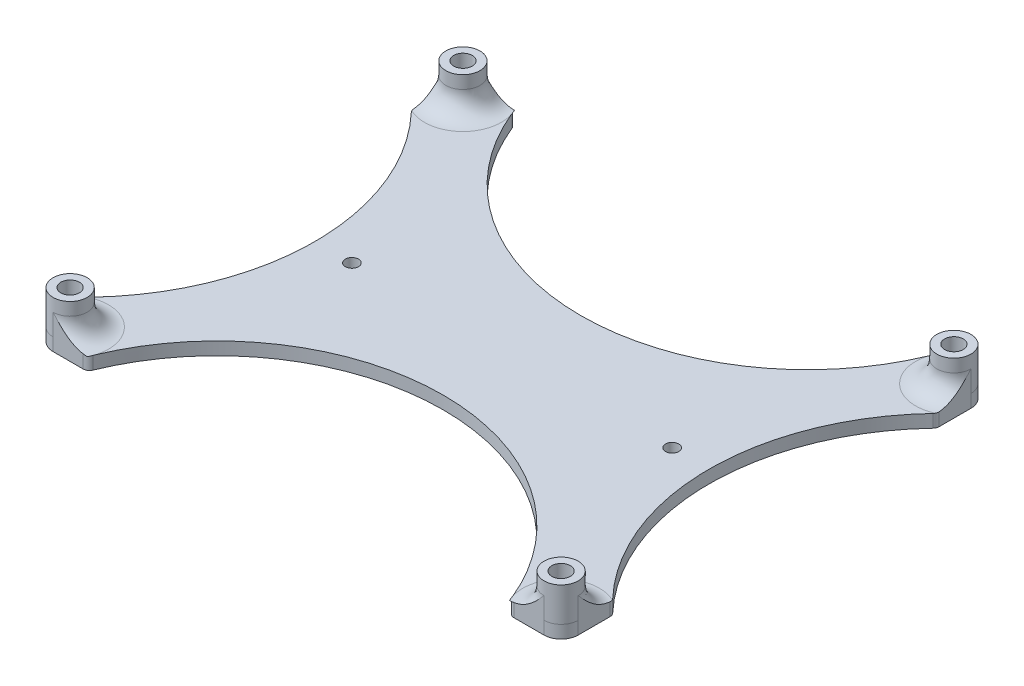
SolidWorks part; units mm, degrees
ref_plane "Alzado" through (0, 0, 0) normal (0, 0, 1) x (1, 0, 0)
ref_plane "Planta" through (0, 0, 0) normal (0, 1, 0) x (1, 0, 0)
ref_plane "Vista lateral" through (0, 0, 0) normal (1, 0, 0) x (0, 0, -1)
sketch "Croquis1" plane through (0, 0, 0) normal (0, 1, 0) x (1, 0, 0)
  line L1 (0, 0) -> (123, 0)
  line L2 (0, 0) -> (0, 100)
  line L3 (0, 100) -> (123, 100)
  line L4 (123, 0) -> (123, 100)
  dimension "D1" = 123
  dimension "D2" = 100
extrude "Saliente-Extruir1" add sketch "Croquis1" along normal blind 3
sketch "Croquis2" plane through (0, 3, 0) normal (0, 1, 0) x (1, 0, 0)
  line L0 (61.5, 100) -> (61.5, 0) construction
  line L1 (123, 100) -> (0, 100) construction
  line L2 (0, 0) -> (123, 0) construction
  line L3 (123, 0) -> (123, 100) construction
  line L4 (4, 4) -> (119, 4) construction
  line L5 (4, 4) -> (4, 96) construction
  line L6 (4, 96) -> (119, 96) construction
  line L7 (119, 4) -> (119, 96) construction
  line L8 (4, 4) -> (119, 96) construction
  line L9 (4, 96) -> (119, 4) construction
  circle A0 centre (4, 96) radius 4
  circle A1 centre (4, 4) radius 4
  circle A2 centre (119, 4) radius 4
  circle A3 centre (119, 96) radius 4
  point P6 (61.5, 50)
  dimension "D1" = 115
  dimension "D2" = 92
extrude "Saliente-Extruir2" add sketch "Croquis2" along normal blind 8
sketch "Croquis3" plane through (0, 11, 0) normal (0, 1, 0) x (1, 0, 0)
  circle A0 centre (4, 4) radius 4 construction
  circle A1 centre (4, 96) radius 4
  circle A2 centre (4, 96) radius 4
  arc A3 (123, 4) -> (119, 0) centre (119, 4) ccw construction
  arc A4 (119, 100) -> (123, 96) centre (119, 96) ccw construction
  circle A5 centre (4, 4) radius 4
  arc A6 (123, 4) -> (119, 0) centre (119, 4) ccw
  arc A7 (119, 100) -> (123, 96) centre (119, 96) ccw
  circle A8 centre (4, 96) radius 2.175
  circle A9 centre (119, 96) radius 2.175
  circle A10 centre (119, 4) radius 2.175
  circle A11 centre (4, 4) radius 2.175
  dimension "D2" = 4.35
  dimension "D1" = 0
extrude "Cortar-Extruir1" cut sketch "Croquis3" against normal blind 4.5 contours A8 | A9 | A10 | A11 region at (4, 11, -96) region at (119, 11, -96) region at (119, 11, -4) region at (4, 11, -4)
fillet "Redondeo1" radius 4 4 edges at (0, 1.5, -100) (123, 1.5, -100) (123, 1.5, 0) (0, 1.5, 0)
fillet "Redondeo2" radius 5 4 edges at (116.1716, 3, -6.8284) (116.1716, 3, -93.1716) (6.8284, 3, -93.1716) (6.8284, 3, -6.8284)
sketch "Croquis4" plane through (0, 3, 0) normal (0, 1, 0) x (1, 0, 0)
  line L0 (0, 50) -> (123, 50) construction
  line L1 (0, 87.9377) -> (0, 12.0623) construction
  line L2 (123, 12.0623) -> (123, 87.9377) construction
  circle A0 centre (24, 50) radius 1.55
  circle A1 centre (99, 50) radius 1.55
  dimension "D2" = 3.1
  dimension "D1" = 75
  dimension "D3" = 24
extrude "Cortar-Extruir2" cut sketch "Croquis4" against normal up to surface (3 mm away) up to face at (61.5, 0, -50)
sketch "Croquis5" plane through (0, 3, 0) normal (0, 1, 0) x (1, 0, 0)
  line L0 (0, 87.9377) -> (0, 12.0623)
  line L1 (12.0623, 100) -> (110.9377, 100)
  line L2 (61.5, 100) -> (61.5, 0) construction
  line L3 (12.0623, 0) -> (110.9377, 0) construction
  line L4 (0, 50) -> (123, 50) construction
  line L5 (123, 12.0623) -> (123, 87.9377) construction
  line L6 (123, 87.9377) -> (123, 12.0623)
  line L7 (12.0623, 0) -> (110.9377, 0)
  arc A0 (12.0623, 100) -> (110.9377, 100) centre (61.5, 119.1195) ccw
  arc A1 (0, 87.9377) -> (0, 12.0623) centre (-39.2296, 50) cw
  arc A2 (123, 87.9377) -> (123, 12.0623) centre (162.2296, 50) ccw
  arc A3 (12.0623, 0) -> (110.9377, 0) centre (61.5, -19.1195) cw
extrude "Cortar-Extruir3" cut sketch "Croquis5" against normal up to surface (3 mm away) up to face at (24, 0, -51.55)
fillet "Redondeo3" radius 1.5 8 edges at (12.0623, 1.5, -100) (0, 1.5, -87.9377) (0, 1.5, -12.0623) (12.0623, 1.5, 0) (110.9377, 1.5, 0) (123, 1.5, -12.0623) (110.9377, 1.5, -100) (123, 1.5, -87.9377)
